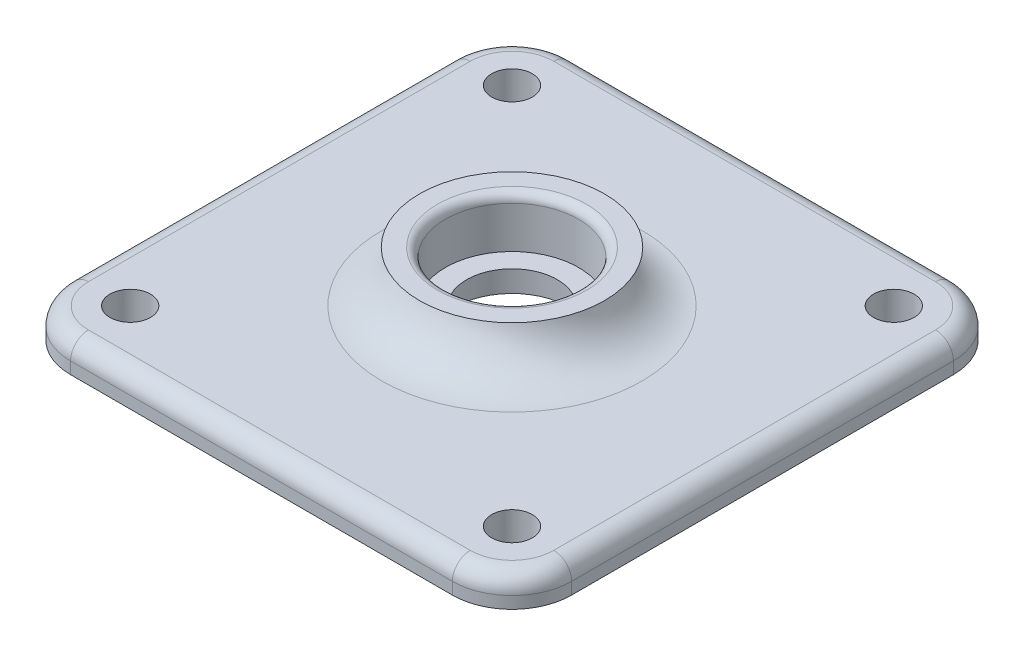
SolidWorks part; units mm, degrees
ref_plane "Front Plane" through (0, 0, 0) normal (0, 0, 1) x (1, 0, 0)
ref_plane "Top Plane" through (0, 0, 0) normal (0, 1, 0) x (1, 0, 0)
ref_plane "Right Plane" through (0, 0, 0) normal (1, 0, 0) x (0, 0, -1)
sketch "Sketch1" plane through (0, 0, 0) normal (0, 1, 0) x (1, 0, 0)
  line L1 (32, 42) -> (-32, 42)
  line L2 (42, 32) -> (42, -32)
  line L3 (32, -42) -> (-32, -42)
  line L4 (-42, 32) -> (-42, -32)
  line L5 (42, 42) -> (-42, -42) construction
  line L6 (42, -42) -> (-42, 42) construction
  arc A0 (32, 42) -> (42, 32) centre (32, 32) cw
  arc A1 (42, -32) -> (32, -42) centre (32, -32) cw
  arc A2 (-32, -42) -> (-42, -32) centre (-32, -32) cw
  arc A3 (-32, 42) -> (-42, 32) centre (-32, 32) ccw
  point P0 (0, 0)
  dimension "D1" = 10
  dimension "D2" = 84
extrude "Boss-Extrude1" add sketch "Sketch1" along normal blind 5 contours L1 A3 L4 A2 L3 A1 L2 A0
sketch "Sketch3" plane through (0, 0, 0) normal (0, 0, 1) x (1, 0, 0)
  line L0 (32, 5) -> (-32, 5) construction
  line L1 (0, 5) -> (-12.5, 5) construction
  line L3 (12.5, 12) -> (-12.5, 12) construction
  line L4 (-12.5, 5) -> (-12.5, 12) construction
  line L5 (-12.5, 5) -> (-11.15, 5)
  line L7 (-12.5, 12) -> (-11.15, 12)
  line L8 (-11.15, 12) -> (-11.15, 5)
  line L9 (-32, 5) -> (-12.5, 5)
  line L10 (0, 0) -> (0, -50000) construction
  line L11 (0, 5) -> (-9.6, 5)
  line L12 (0, 5) -> (0, 0)
  line L13 (-9.6, 5) -> (-9.6, 0)
  line L14 (32, 0) -> (-32, 0) construction
  line L15 (-9.6, 0) -> (0, 0)
  line L16 (-12.5, 13.5) -> (-12.5, 12) construction
  line L17 (-15.5, 9.75) -> (-15.5, 13.5) construction
  line L19 (-15.5, 13.5) -> (-12.5, 13.5)
  arc A0 (-12.5, 12) -> (-22.25, 5) centre (-22.0401, 14.9978) cw
  arc A1 (-15.5, 13.5) -> (-12.5, 12) centre (-15.5, 9.75) cw
  arc A2 (-12.5, 13.5) -> (-11.15, 12) centre (-12.6583, 12) cw
  arc A3 (-9.6, 0) -> (-7.6, 5) centre (-7.3717, 2.0087) cw
  dimension "D4" = 10
  dimension "D8" = 3
  dimension "D1" = 12.5
  dimension "D2" = 7
  dimension "D3" = 11.15
  dimension "D5" = 9.6
  dimension "D6" = 1.5
  dimension "D7" = 3
  dimension "D9" = 2
revolve "Revolve2" add sketch "Sketch3" angle 360 about L10 region at (-13.6934, 7.4314, 0) region at (-12.5314, 12.832, 0)
revolve "Cut-Revolve2" cut sketch "Sketch3<5>" angle 360 about L10 region at (-4.7402, 2.4691, 0)
sketch "Sketch3<5>" plane through (0, 0, 0) normal (0, 0, 1) x (1, 0, 0) same geometry as "Sketch3"
fillet "Fillet1" radius 3 8 edges at (42, 5, 0) (39.0711, 5, -39.0711) (0, 5, -42) (-39.0711, 5, -39.0711) (-42, 5, 0) (-39.0711, 5, 39.0711) (0, 5, 42) (39.0711, 5, 39.0711)
sketch "Sketch13" plane through (0, 5, 0) normal (0, 1, 0) x (1, 0, 0)
  line L1 (32, 32) -> (-32, 32) construction
  line L2 (32, 32) -> (32, -32) construction
  line L3 (32, -32) -> (-32, -32) construction
  line L4 (-32, 32) -> (-32, -32) construction
  line L5 (32, 32) -> (-32, -32) construction
  line L6 (32, -32) -> (-32, 32) construction
  point P0 (0, 0)
  dimension "D1" = 64
hole_wizard "Tap Drill for M8x1.25 Tap1" positions "Sketch16" profile "Sketch18" hole size "M8x1.25" standard "ANSI Metric"
sketch "Sketch16" plane through (0, 5, 0) normal (0, 1, 0) x (1, 0, 0)
  point P0 (-32, 32)
  point P3 (-32, -32)
  point P6 (32, -32)
  point P9 (32, 32)
sketch "Sketch18" plane through (-32, 5, -32) normal (1, 0, 0) x (0, 0, 1)
  line L0 (0, 0) -> (0, 10.0429)
  line L1 (0, 10.0429) -> (3.4, 8)
  line L2 (3.4, 8) -> (3.4, 0)
  line L5 (3.4, 0) -> (0, 0)
  line L10 (0, 10.0429) -> (-3.4, 8) construction
  line L11 (0, -6.35) -> (0, 107.95) construction
  dimension "Hole Dia." = 6.8
  dimension "Hole Depth" = 8
  dimension "Drill Angle" = 118
